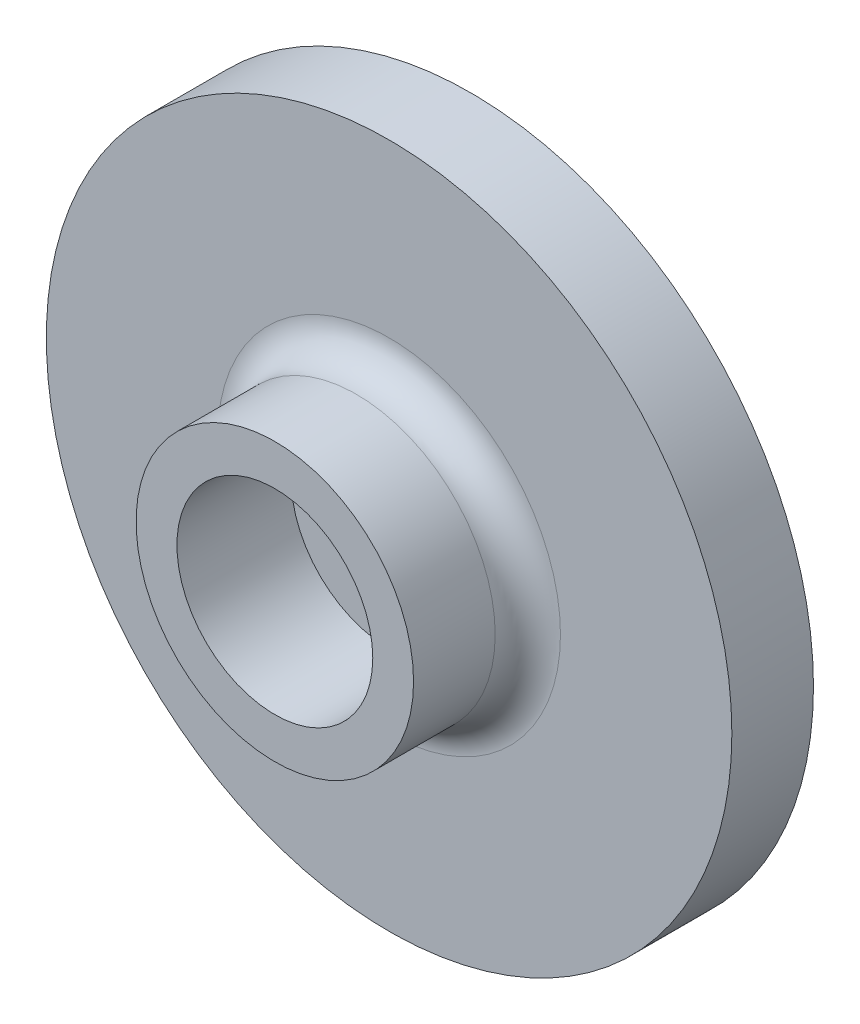
SolidWorks part; units mm, degrees
ref_plane "Front Plane" through (0, 0, 0) normal (0, 0, 1) x (1, 0, 0)
ref_plane "Top Plane" through (0, 0, 0) normal (0, 1, 0) x (1, 0, 0)
ref_plane "Right Plane" through (0, 0, 0) normal (1, 0, 0) x (0, 0, -1)
sketch "Sketch1" plane through (0, 0, 0) normal (0, 0, 1) x (1, 0, 0)
  circle A0 centre (0, 0) radius 10.5
  dimension "D1" = 21
extrude "Boss-Extrude1" add sketch "Sketch1" along normal blind 2.5
sketch "Sketch2" plane through (0, 0, 2.5) normal (0, 0, 1) x (1, 0, 0)
  circle A0 centre (0, 0) radius 4.25
  circle A1 centre (0, 0) radius 3
  circle A2 centre (0, 0) radius 1.5
  dimension "D1" = 8.5
  dimension "D2" = 6
  dimension "D3" = 3
extrude "Boss-Extrude2" add sketch "Sketch2" along normal blind 3.5 contours A0 A1 region at (-4.1298, 0, 2.5)
extrude "Cut-Extrude1" cut sketch "Sketch2<3>" against normal blind 3.5 contours A2 region at (0, 0, 2.5)
sketch "Sketch2<3>" plane through (0, 0, 2.5) normal (0, 0, 1) x (1, 0, 0) same geometry as "Sketch2"
fillet "Fillet1" radius 1 1 edges at (4.25, 0, 2.5)
sketch "Sketch3" plane through (0, 0, 0) normal (0, 0, -1) x (-1, 0, 0)
  circle A0 centre (0, 0) radius 3
extrude "Cut-Extrude2" cut sketch "Sketch3" against normal blind 1
